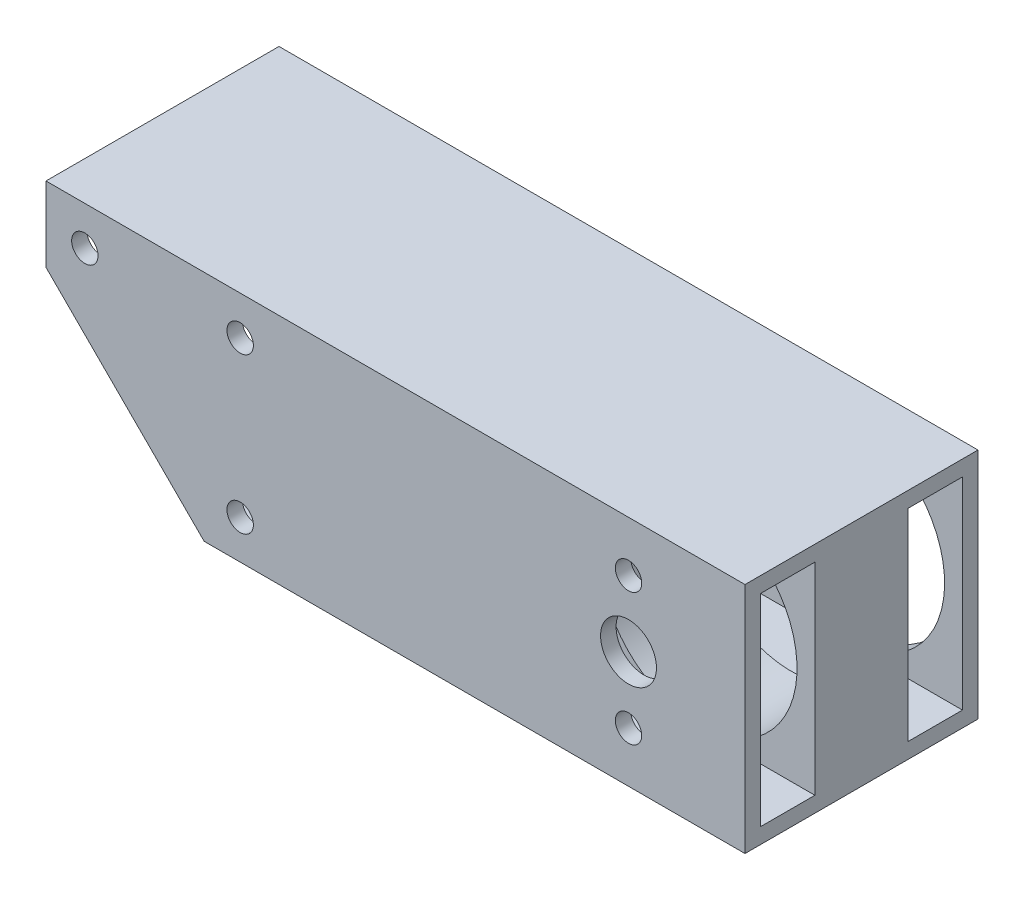
SolidWorks part; units mm, degrees
material "PLA 15%"
ref_plane "Front Plane" through (0, 0, 0) normal (0, 0, 1) x (1, 0, 0)
ref_plane "Top Plane" through (0, 0, 0) normal (0, 1, 0) x (1, 0, 0)
ref_plane "Right Plane" through (0, 0, 0) normal (1, 0, 0) x (0, 0, -1)
sketch "Sketch1" plane through (0, 0, 0) normal (1, 0, 0) x (0, 0, -1)
  line L1 (-15, -15) -> (15, -15)
  line L2 (-15, -15) -> (-15, 15)
  line L3 (-15, 15) -> (15, 15)
  line L4 (15, -15) -> (15, 15)
  line L5 (-15, -15) -> (15, 15) construction
  line L6 (-15, 15) -> (15, -15) construction
  line L11 (-5.1844, 5.1844) -> (5.1844, -5.1844) construction
  line L12 (-5.1844, -5.1844) -> (5.1844, 5.1844) construction
  line L13 (-13, 13) -> (-6, 13)
  line L14 (-13, 13) -> (-13, -13)
  line L15 (-13, -13) -> (-6, -13)
  line L16 (-6, 13) -> (-6, -13)
  line L17 (13, 13) -> (6, 13)
  line L18 (13, 13) -> (13, -13)
  line L19 (13, -13) -> (6, -13)
  line L20 (6, 13) -> (6, -13)
  point P0 (0, 0)
  point P7 (0, 0)
  dimension "D1" = 30
  dimension "D2" = 30
  dimension "D3" = 2
  dimension "D4" = 7
  dimension "D5" = 2
  dimension "D6" = 7
  dimension "D7" = 2
  dimension "D8" = 2
extrude "Boss-Extrude3" add sketch "Sketch1" along normal blind 90
sketch "Sketch6" plane through (0, 0, -15) normal (0, 0, -1) x (-1, 0, 0)
  line L0 (-90, -15) -> (-90, 15) construction
  circle A0 centre (-75, 0) radius 12.7
  dimension "D2" = 25.4
  dimension "D1" = 15
extrude "Cut-Extrude5" cut sketch "Sketch6" against normal blind 23
sketch "Sketch8" plane through (0, 0, 15) normal (0, 0, 1) x (1, 0, 0)
  line L0 (90, 15) -> (90, -15) construction
  line L1 (75, 0) -> (90, 0) construction
  circle A0 centre (75, 0) radius 3.6
  circle A1 centre (75, 8.5) radius 1.7
  circle A2 centre (75, -8.5) radius 1.7
  dimension "D2" = 7.2
  dimension "D5" = 3.4
  dimension "D1" = 15
  dimension "D3" = 17
extrude "Cut-Extrude6" cut sketch "Sketch8" against normal blind 17
sketch "Sketch9" plane through (0, 0, 0) normal (-1, 0, 0) x (0, 0, 1)
  line L0 (-6, 13) -> (6, 13)
  line L1 (-6, -13) -> (6, -13)
  line L2 (-6, 13) -> (-6, -13)
  line L3 (6, 13) -> (6, -13)
extrude "Cut-Extrude7" cut sketch "Sketch9" against normal blind 59
sketch "Sketch11" plane through (0, 0, 15) normal (0, 0, 1) x (1, 0, 0)
  line L13 (25, 10) -> (25, -10) construction
  line L16 (5, -10) -> (90, -10)
  line L17 (5, 10) -> (5, -10)
  line L18 (90, 10) -> (5, 10)
  line L19 (5, -10) -> (25, -10) construction
  line L20 (5, 10) -> (5, -10) construction
  line L21 (25, 10) -> (5, 10) construction
  point P12 (5, -10)
  point P14 (25, -10)
  point P15 (5, 10)
  point P16 (25, 10)
  dimension "D1" = 5
hole_wizard "M3 Clearance Hole1" positions "Sketch11" profile "Sketch12" hole size "M3" standard "ANSI Metric" end condition through all
sketch "Sketch12" plane through (25, 10, 15) normal (1, 0, 0) x (0, -1, 0)
  line L0 (0, 0) -> (0, 30)
  line L1 (0, 30) -> (1.7, 30)
  line L2 (1.7, 30) -> (1.7, 0)
  line L5 (1.7, 0) -> (0, 0)
  line L11 (0, -6.35) -> (0, 107.95) construction
  dimension "Thru Hole Dia." = 3.4
  dimension "Thru Hole Depth" = 30
sketch "Sketch13" plane through (0, 0, 0) normal (0, 0, 1) x (1, 0, 0)
  line L0 (0, -5.3647) -> (20.3647, 15)
  line L1 (0, 15) -> (0, -15) construction
  line L2 (90, 15) -> (0, 15) construction
  line L3 (20.3647, 15) -> (0, 15)
  line L4 (0, 15) -> (0, -5.3647)
  line L5 (0, 0) -> (90, 0) construction
  line L6 (90, 15) -> (90, -15) construction
  line L7 (0, -15) -> (0, 5.3647)
  line L8 (20.3647, -15) -> (0, -15)
  line L9 (0, 5.3647) -> (20.3647, -15)
  dimension "D1" = 45
  dimension "D2" = 28.8
extrude "Cut-Extrude8" cut sketch "Sketch13" against normal blind 26 and the other way blind 28 contours L9 L0 L7 L8 | L5 L7 L0 | L4 L5 L9 region at (1.7882, -1.7882, 0) region at (7.594, -9.5352, 0) region at (1.7882, 1.7882, 0)
